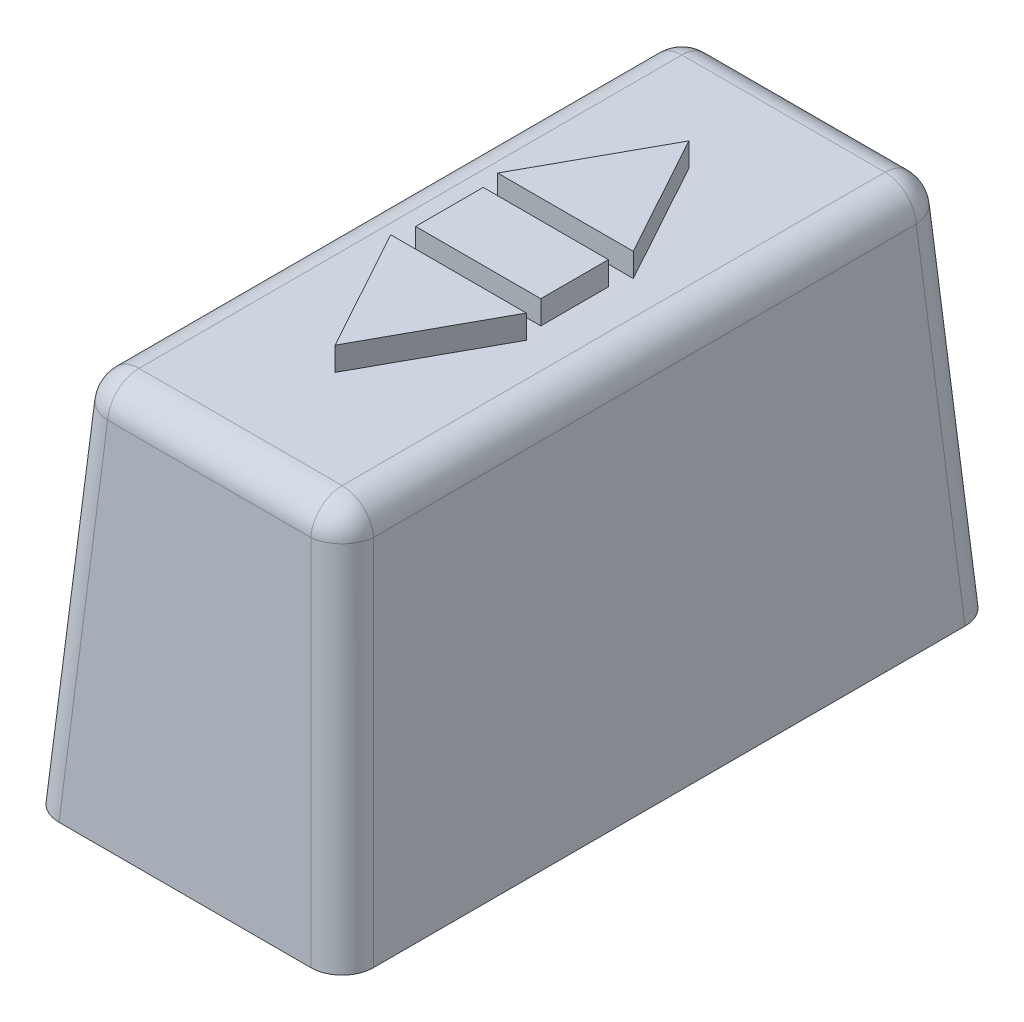
SolidWorks part; units mm, degrees
ref_plane "Front Plane" through (0, 0, 0) normal (0, 0, 1) x (1, 0, 0)
ref_plane "Top Plane" through (0, 0, 0) normal (0, 1, 0) x (1, 0, 0)
ref_plane "Right Plane" through (0, 0, 0) normal (1, 0, 0) x (0, 0, -1)
sketch "Sketch1" plane through (0, 0, 0) normal (0, 1, 0) x (1, 0, 0)
  line L0 (0, 22.5) -> (-8.6205, 6.8)
  line L1 (-20, 41.6) -> (20, 41.6)
  line L2 (-20, 41.6) -> (-20, -41.6)
  line L3 (-20, -41.6) -> (20, -41.6)
  line L4 (20, 41.6) -> (20, -41.6)
  line L5 (-8.6205, 6.8) -> (8.6205, 6.8)
  line L6 (8.6205, 6.8) -> (0, 22.5)
  line L7 (0, 22.5) -> (0, 6.8) construction
  line L8 (-8.6205, 6.8) -> (0, 22.5)
  line L9 (-7.9583, 4.3) -> (7.9583, 4.3)
  line L10 (-7.9583, 4.3) -> (-7.9583, -4.3)
  line L11 (-7.9583, -4.3) -> (7.9583, -4.3)
  line L12 (7.9583, 4.3) -> (7.9583, -4.3)
  line L13 (0, 22.5) -> (8.6205, 6.8)
  line L14 (-55, 0) -> (55, 0) construction
  line L15 (0, -22.5) -> (0, -6.8) construction
  line L16 (0, -22.5) -> (8.6205, -6.8)
  line L17 (-8.6205, -6.8) -> (0, -22.5)
  line L18 (8.6205, -6.8) -> (0, -22.5)
  line L19 (-8.6205, -6.8) -> (8.6205, -6.8)
  line L20 (0, -22.5) -> (-8.6205, -6.8)
  point P4 (0, 41.6)
  point P6 (20, 0)
  point P9 (0, 6.8)
  point P16 (7.9583, 0)
  point P17 (0, 4.3)
  dimension "D1" = 83.2
  dimension "D2" = 40
  dimension "D3" = 45
  dimension "D4" = 8.6
  dimension "D5" = 15.7
extrude "Boss-Extrude1" add sketch "Sketch1" along normal blind 48 contours L4 L1 L2 L3 L6 L5 L0 L9 L12 L11 L10 L17 L19 L16 | L5 L6 L0 | L12 L9 L10 L11 | L19 L17 L16 region at (0, 0, -12.0333) region at (0, 0, -40.6768) region at (0, 0, 0) region at (0, 0, 12.0333)
chamfer "Chamfer1" distance 48 angle 4 4 edges at (0, 48, 41.6) (-20, 48, 0) (0, 48, -41.6) (20, 48, 0) first distance on face at (0, 24, 41.6) first distance on face at (-20, 24, 0) first distance on face at (0, 24, -41.6) first distance on face at (20, 24, 0)
extrude "Boss-Extrude2" add sketch "Sketch1<3>" along normal blind 3 from surface contours L5 L6 L0 | L12 L9 L10 L11 | L19 L17 L16 region at (0, 0, -12.0333) region at (0, 0, 0) region at (0, 0, 12.0333) starting at face at (0, 48, 0)
sketch "Sketch1<3>" plane through (0, 0, 0) normal (0, 1, 0) x (1, 0, 0) same geometry as "Sketch1"
fillet "Fillet1" radius 4 8 edges at (-18.3218, 24, 39.9218) (0, 48, 38.2435) (18.3218, 24, 39.9218) (16.6435, 48, 0) (0, 48, -38.2435) (18.3218, 24, -39.9218) (-18.3218, 24, -39.9218) (-16.6435, 48, 0)
